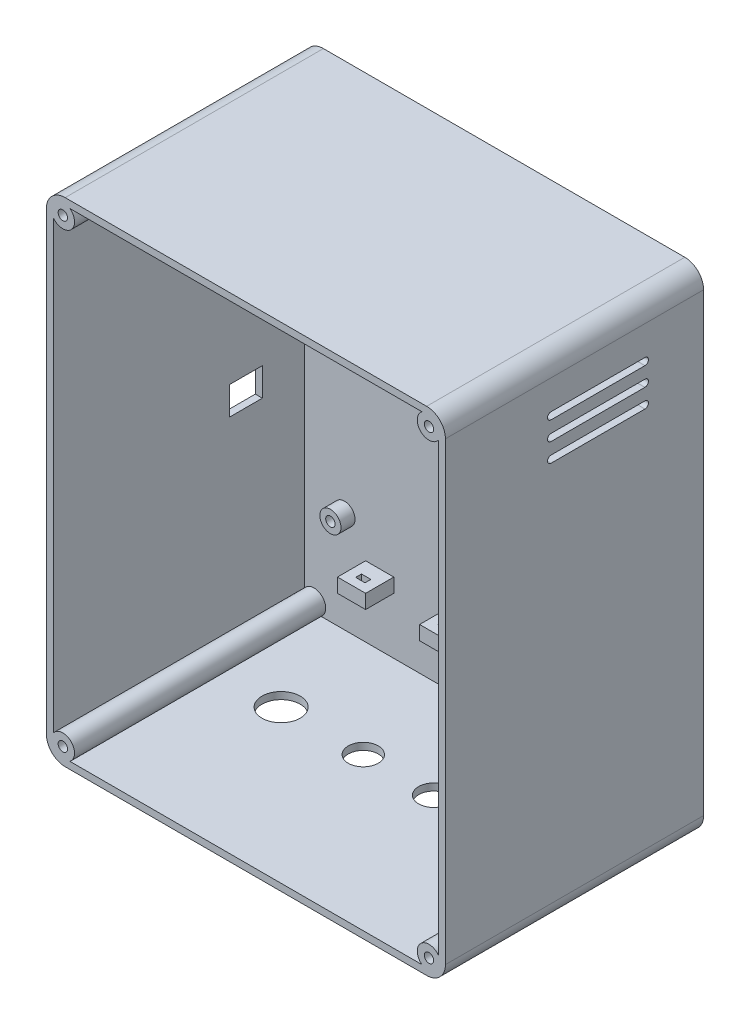
SolidWorks part; units mm, degrees
ref_plane "Front Plane" through (0, 0, 0) normal (0, 0, 1) x (1, 0, 0)
ref_plane "Top Plane" through (0, 0, 0) normal (0, 1, 0) x (1, 0, 0)
ref_plane "Right Plane" through (0, 0, 0) normal (1, 0, 0) x (0, 0, -1)
sketch "Sketch1" plane through (0, 0, 0) normal (0, 0, 1) x (1, 0, 0)
  line L0 (-77, 0) -> (77, 0)
  line L1 (85, 8) -> (85, 202)
  line L2 (77, 210) -> (-77, 210)
  line L3 (-85, 202) -> (-85, 8)
  arc A0 (-85, 8) -> (-77, 0) centre (-77, 8) ccw
  arc A1 (77, 0) -> (85, 8) centre (77, 8) ccw
  arc A2 (85, 202) -> (77, 210) centre (77, 202) ccw
  arc A3 (-77, 210) -> (-85, 202) centre (-77, 202) ccw
extrude "Block" add sketch "Sketch1" along normal blind 110
shell "Shell1" thickness 3 removed face at (0, 105, 110)
sketch "Sketch2" plane through (0, 0, 0) normal (0, 0, 1) x (1, 0, 0)
  circle A0 centre (-78, 7) radius 5
  circle A1 centre (78, 7) radius 5
  circle A2 centre (-78, 203) radius 5
  circle A3 centre (78, 203) radius 5
extrude "Corner columns" add sketch "Sketch2" along normal blind 110
ref_plane "P1_Front_110" through (0, 0, 110) normal (0, 0, 1) x (1, 0, 0)
sketch "Sketch3" plane through (0, 0, 110) normal (0, 0, 1) x (1, 0, 0)
  circle A0 centre (-78, 7) radius 2
  circle A1 centre (78, 7) radius 2
  circle A2 centre (-78, 203) radius 2
  circle A3 centre (78, 203) radius 2
extrude "Front panel insert holes" cut sketch "Sketch3" against normal blind 7
ref_plane "P2_Front_3" through (0, 0, 3) normal (0, 0, 1) x (1, 0, 0)
sketch "Sketch4" plane through (0, 0, 3) normal (0, 0, 1) x (1, 0, 0)
  circle A0 centre (-65, 46) radius 4.5
  circle A1 centre (65, 46) radius 4.5
  circle A2 centre (-65, 190) radius 4.5
  circle A3 centre (65, 190) radius 4.5
extrude "Plate bosses" add sketch "Sketch4" along normal blind 6
ref_plane "P3_Front_9" through (0, 0, 9) normal (0, 0, 1) x (1, 0, 0)
sketch "Sketch5" plane through (0, 0, 9) normal (0, 0, 1) x (1, 0, 0)
  circle A0 centre (-65, 46) radius 2
  circle A1 centre (65, 46) radius 2
  circle A2 centre (-65, 190) radius 2
  circle A3 centre (65, 190) radius 2
extrude "Plate insert holes" cut sketch "Sketch5" against normal blind 7
sketch "Sketch6" plane through (0, 0, 0) normal (0, 1, 0) x (1, 0, 0)
  circle A0 centre (-50, -45) radius 8.15
  circle A1 centre (-15, -45) radius 6.4
  circle A2 centre (15, -45) radius 6.4
  circle A3 centre (50, -45) radius 6.4
extrude "Cable gland holes" cut sketch "Sketch6" along normal blind 4
sketch "Sketch7" plane through (0, 0, 3) normal (0, 0, 1) x (1, 0, 0)
  line L1 (-56, 27) -> (-44, 27)
  line L2 (-56, 27) -> (-56, 33)
  line L3 (-56, 33) -> (-44, 33)
  line L4 (-44, 27) -> (-44, 33)
  line L5 (-56, 27) -> (-44, 33) construction
  line L6 (-56, 33) -> (-44, 27) construction
  line L7 (-21, 27) -> (-9, 27)
  line L8 (-21, 27) -> (-21, 33)
  line L9 (-21, 33) -> (-9, 33)
  line L10 (-9, 27) -> (-9, 33)
  line L11 (-21, 27) -> (-9, 33) construction
  line L12 (-21, 33) -> (-9, 27) construction
  line L13 (9, 27) -> (21, 27)
  line L14 (9, 27) -> (9, 33)
  line L15 (9, 33) -> (21, 33)
  line L16 (21, 27) -> (21, 33)
  line L17 (9, 27) -> (21, 33) construction
  line L18 (9, 33) -> (21, 27) construction
  line L19 (44, 27) -> (56, 27)
  line L20 (44, 27) -> (44, 33)
  line L21 (44, 33) -> (56, 33)
  line L22 (56, 27) -> (56, 33)
  line L23 (44, 27) -> (56, 33) construction
  line L24 (44, 33) -> (56, 27) construction
  point P0 (-50, 30)
  point P5 (-15, 30)
  point P10 (15, 30)
  point P15 (50, 30)
extrude "Cable tie bars" add sketch "Sketch7" along normal blind 12
ref_plane "P4_Top_26.99" through (0, 26.99, 0) normal (0, 1, 0) x (1, 0, 0)
sketch "Sketch8" plane through (0, 26.99, 0) normal (0, 1, 0) x (1, 0, 0)
  line L1 (-52, -11.25) -> (-48, -11.25)
  line L2 (-52, -11.25) -> (-52, -8.75)
  line L3 (-52, -8.75) -> (-48, -8.75)
  line L4 (-48, -11.25) -> (-48, -8.75)
  line L5 (-52, -11.25) -> (-48, -8.75) construction
  line L6 (-52, -8.75) -> (-48, -11.25) construction
  line L7 (-17, -11.25) -> (-13, -11.25)
  line L8 (-17, -11.25) -> (-17, -8.75)
  line L9 (-17, -8.75) -> (-13, -8.75)
  line L10 (-13, -11.25) -> (-13, -8.75)
  line L11 (-17, -11.25) -> (-13, -8.75) construction
  line L12 (-17, -8.75) -> (-13, -11.25) construction
  line L13 (13, -11.25) -> (17, -11.25)
  line L14 (13, -11.25) -> (13, -8.75)
  line L15 (13, -8.75) -> (17, -8.75)
  line L16 (17, -11.25) -> (17, -8.75)
  line L17 (13, -11.25) -> (17, -8.75) construction
  line L18 (13, -8.75) -> (17, -11.25) construction
  line L19 (48, -11.25) -> (52, -11.25)
  line L20 (48, -11.25) -> (48, -8.75)
  line L21 (48, -8.75) -> (52, -8.75)
  line L22 (52, -11.25) -> (52, -8.75)
  line L23 (48, -11.25) -> (52, -8.75) construction
  line L24 (48, -8.75) -> (52, -11.25) construction
  point P0 (-50, -10)
  point P5 (-15, -10)
  point P10 (15, -10)
  point P15 (50, -10)
extrude "Cable tie slots" cut sketch "Sketch8" along normal blind 6.02
ref_plane "P5_Right_-85" through (-85, 0, 0) normal (1, 0, 0) x (0, 0, -1)
sketch "Sketch9" plane through (-85, 0, 0) normal (1, 0, 0) x (0, 0, -1)
  line L1 (-35, 89) -> (-21, 89)
  line L2 (-35, 89) -> (-35, 101)
  line L3 (-35, 101) -> (-21, 101)
  line L4 (-21, 89) -> (-21, 101)
  line L5 (-35, 89) -> (-21, 101) construction
  line L6 (-35, 101) -> (-21, 89) construction
  point P0 (-28, 95)
extrude "USB access" cut sketch "Sketch9" along normal blind 4
ref_plane "P6_Right_-85" through (-85, 0, 0) normal (1, 0, 0) x (0, 0, -1)
sketch "Sketch10" plane through (-85, 0, 0) normal (1, 0, 0) x (0, 0, -1)
  line L0 (-25, 172) -> (-65, 172) construction
  line L1 (-25, 170.5) -> (-65, 170.5)
  line L2 (-25, 173.5) -> (-65, 173.5)
  line L3 (-25, 180) -> (-65, 180) construction
  line L4 (-25, 178.5) -> (-65, 178.5)
  line L5 (-25, 181.5) -> (-65, 181.5)
  line L6 (-25, 188) -> (-65, 188) construction
  line L7 (-25, 186.5) -> (-65, 186.5)
  line L8 (-25, 189.5) -> (-65, 189.5)
  arc A0 (-25, 170.5) -> (-25, 173.5) centre (-25, 172) ccw
  arc A1 (-65, 173.5) -> (-65, 170.5) centre (-65, 172) ccw
  arc A2 (-25, 178.5) -> (-25, 181.5) centre (-25, 180) ccw
  arc A3 (-65, 181.5) -> (-65, 178.5) centre (-65, 180) ccw
  arc A4 (-25, 186.5) -> (-25, 189.5) centre (-25, 188) ccw
  arc A5 (-65, 189.5) -> (-65, 186.5) centre (-65, 188) ccw
  point P2 (-45, 172)
  point P7 (-45, 180)
  point P14 (-45, 188)
  point P21 (0, 0)
extrude "Vents left" cut sketch "Sketch10" along normal blind 4
ref_plane "P7_Right_85" through (85, 0, 0) normal (1, 0, 0) x (0, 0, -1)
sketch "Sketch11" plane through (85, 0, 0) normal (1, 0, 0) x (0, 0, -1)
  line L0 (-25, 172) -> (-65, 172) construction
  line L1 (-25, 170.5) -> (-65, 170.5)
  line L2 (-25, 173.5) -> (-65, 173.5)
  line L3 (-25, 180) -> (-65, 180) construction
  line L4 (-25, 178.5) -> (-65, 178.5)
  line L5 (-25, 181.5) -> (-65, 181.5)
  line L6 (-25, 188) -> (-65, 188) construction
  line L7 (-25, 186.5) -> (-65, 186.5)
  line L8 (-25, 189.5) -> (-65, 189.5)
  arc A0 (-25, 170.5) -> (-25, 173.5) centre (-25, 172) ccw
  arc A1 (-65, 173.5) -> (-65, 170.5) centre (-65, 172) ccw
  arc A2 (-25, 178.5) -> (-25, 181.5) centre (-25, 180) ccw
  arc A3 (-65, 181.5) -> (-65, 178.5) centre (-65, 180) ccw
  arc A4 (-25, 186.5) -> (-25, 189.5) centre (-25, 188) ccw
  arc A5 (-65, 189.5) -> (-65, 186.5) centre (-65, 188) ccw
  point P2 (-45, 172)
  point P7 (-45, 180)
  point P14 (-45, 188)
  point P21 (0, 0)
extrude "Vents right" cut sketch "Sketch11" against normal blind 4
sketch "Sketch12" plane through (0, 0, 0) normal (0, 0, 1) x (1, 0, 0)
  circle A0 centre (-45, 165) radius 4.75
  circle A1 centre (45, 165) radius 4.75
extrude "Keyhole heads" cut sketch "Sketch12" along normal blind 4
sketch "Sketch13" plane through (0, 0, 0) normal (0, 0, 1) x (1, 0, 0)
  line L0 (-45, 165) -> (-45, 176) construction
  line L1 (-47.15, 165) -> (-47.15, 176)
  line L2 (-42.85, 165) -> (-42.85, 176)
  line L3 (45, 165) -> (45, 176) construction
  line L4 (42.85, 165) -> (42.85, 176)
  line L5 (47.15, 165) -> (47.15, 176)
  arc A0 (-47.15, 165) -> (-42.85, 165) centre (-45, 165) ccw
  arc A1 (-42.85, 176) -> (-47.15, 176) centre (-45, 176) ccw
  arc A2 (42.85, 165) -> (47.15, 165) centre (45, 165) ccw
  arc A3 (47.15, 176) -> (42.85, 176) centre (45, 176) ccw
  point P2 (-45, 170.5)
  point P7 (45, 170.5)
  point P14 (0, 0)
extrude "Keyhole slots" cut sketch "Sketch13" along normal blind 4
